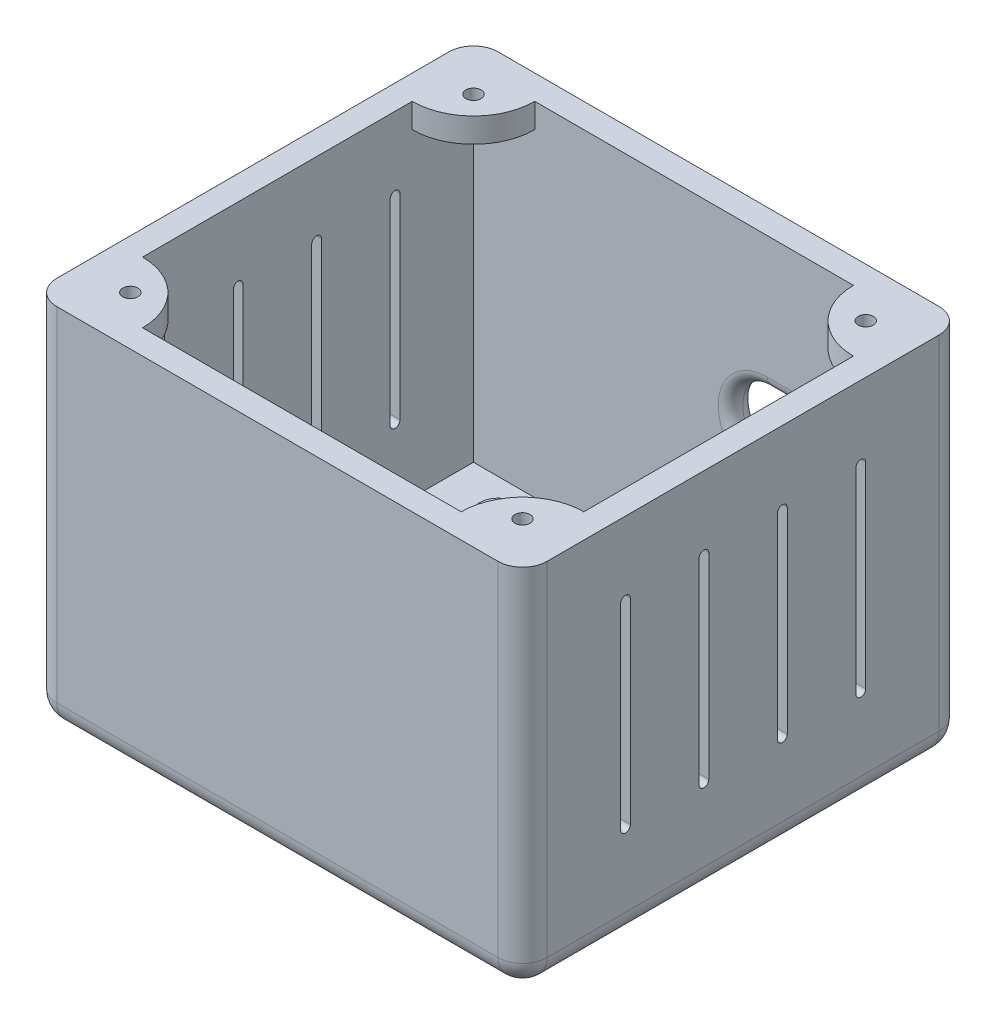
SolidWorks part; units mm, degrees
ref_plane "Front Plane" through (0, 0, 0) normal (0, 0, 1) x (1, 0, 0)
ref_plane "Top Plane" through (0, 0, 0) normal (0, 1, 0) x (1, 0, 0)
ref_plane "Right Plane" through (0, 0, 0) normal (1, 0, 0) x (0, 0, -1)
sketch "Sketch1" plane through (0, 0, 0) normal (0, 1, 0) x (1, 0, 0)
  line L0 (-5, 0) -> (0, 0) construction
  line L1 (0, 0) -> (90, 0)
  line L2 (0, 0) -> (0, 80)
  line L3 (0, 80) -> (90, 80)
  line L4 (90, 0) -> (90, 80)
  line L5 (-5, 85) -> (95, 85)
  line L6 (-5, 85) -> (-5, -5)
  line L7 (-5, -5) -> (95, -5)
  line L8 (95, 85) -> (95, -5)
  line L9 (0, 0) -> (0, -5) construction
  line L10 (90, 85) -> (90, 80) construction
  line L11 (90, 80) -> (95, 80) construction
  dimension "D1" = 90
  dimension "D2" = 5
  dimension "D3" = 80
extrude "Boss-Extrude1" add sketch "Sketch1" along normal blind 70
sketch "Sketch2" plane through (0, 0, 0) normal (0, -1, 0) x (-1, 0, 0)
  line L1 (5, -5) -> (-95, -5)
  line L2 (5, -5) -> (5, 85)
  line L3 (5, 85) -> (-95, 85)
  line L4 (-95, -5) -> (-95, 85)
extrude "Boss-Extrude2" add sketch "Sketch2" along normal blind 5
fillet "Fillet1" radius 5 4 edges at (-5, 32.5, -85) (95, 32.5, -85) (95, 32.5, 5) (-5, 32.5, 5)
sketch "Sketch3" plane through (0, 0, 0) normal (0, 1, 0) x (1, 0, 0)
  line L0 (16.5, 68.5) -> (16.5, 80) construction
  line L1 (90, 80) -> (0, 80) construction
  line L2 (16.5, 80) -> (0, 80) construction
  line L3 (73.5, 11.5) -> (73.5, 0) construction
  line L4 (0, 0) -> (90, 0) construction
  line L5 (73.5, 0) -> (90, 0) construction
  circle A0 centre (16.5, 68.5) radius 1.55
  circle A1 centre (16.5, 11.5) radius 1.55
  circle A2 centre (73.5, 11.5) radius 1.55
  circle A3 centre (73.5, 68.5) radius 1.55
  dimension "D3" = 3.1
  dimension "D1" = 57
  dimension "D2" = 57
extrude "Cut-Extrude1" cut sketch "Sketch3" against normal through all
sketch "Sketch4" plane through (0, -5, 0) normal (0, -1, 0) x (-1, 0, 0)
  circle A0 centre (-16.5, 11.5) radius 3
  circle A1 centre (-73.5, 11.5) radius 3
  circle A2 centre (-73.5, 68.5) radius 3
  circle A3 centre (-16.5, 68.5) radius 3
  dimension "D1" = 6
extrude "Cut-Extrude2" cut sketch "Sketch4" against normal blind 2.5
sketch "Sketch5" plane through (0, 0, 0) normal (0, 1, 0) x (1, 0, 0)
  line L0 (25, 65) -> (25, 15) construction
  line L1 (26, 65) -> (26, 15)
  line L2 (24, 65) -> (24, 15)
  line L3 (25, 65) -> (25, 80) construction
  line L6 (90, 80) -> (0, 80) construction
  line L7 (25, 15) -> (25, 0) construction
  line L8 (0, 0) -> (90, 0) construction
  line L9 (65, 65) -> (65, 15) construction
  line L11 (66, 65) -> (66, 15)
  line L12 (64, 65) -> (64, 15)
  line L13 (65, 65) -> (65, 80) construction
  line L14 (65, 15) -> (65, 0) construction
  line L15 (90, 80) -> (0, 80) construction
  line L16 (0, 0) -> (90, 0) construction
  line L17 (24, 65) -> (26, 65) construction
  line L18 (51.6667, 65) -> (51.6667, 15) construction
  line L19 (52.6667, 65) -> (52.6667, 15)
  line L20 (50.6667, 65) -> (50.6667, 15)
  line L21 (51.6667, 65) -> (51.6667, 80) construction
  line L22 (51.6667, 15) -> (51.6667, 0) construction
  line L23 (38.3333, 65) -> (38.3333, 15) construction
  line L24 (39.3333, 65) -> (39.3333, 15)
  line L25 (37.3333, 65) -> (37.3333, 15)
  line L26 (38.3333, 65) -> (38.3333, 80) construction
  line L27 (38.3333, 15) -> (38.3333, 0) construction
  line L28 (51.6667, 80) -> (65, 80) construction
  line L29 (38.3333, 80) -> (25, 80) construction
  line L30 (38.3333, 80) -> (51.6667, 80) construction
  line L31 (37.3333, 65) -> (39.3333, 65) construction
  line L32 (50.6667, 65) -> (52.6667, 65) construction
  line L33 (64, 65) -> (66, 65) construction
  line L34 (65, 80) -> (90, 80) construction
  line L35 (25, 80) -> (0, 80) construction
  arc A0 (26, 65) -> (24, 65) centre (25, 65) ccw
  arc A1 (24, 15) -> (26, 15) centre (25, 15) ccw
  arc A2 (66, 65) -> (64, 65) centre (65, 65) ccw
  arc A3 (64, 15) -> (66, 15) centre (65, 15) ccw
  arc A4 (52.6667, 65) -> (50.6667, 65) centre (51.6667, 65) ccw
  arc A5 (50.6667, 15) -> (52.6667, 15) centre (51.6667, 15) ccw
  arc A6 (39.3333, 65) -> (37.3333, 65) centre (38.3333, 65) ccw
  arc A7 (37.3333, 15) -> (39.3333, 15) centre (38.3333, 15) ccw
  point P2 (25, 40)
  point P19 (65, 40)
  point P37 (51.6667, 40)
  point P48 (38.3333, 40)
  dimension "D1" = 1
  dimension "D2" = 15
  dimension "D3" = 25
extrude "Cut-Extrude3" cut sketch "Sketch5" against normal through all
sketch "Sketch6" plane through (0, 0, -80) normal (0, 0, 1) x (1, 0, 0)
  line L0 (0, 70) -> (12.5, 70)
  line L1 (90, 70) -> (0, 70) construction
  line L3 (0, 70) -> (0, 0) construction
  line L4 (0, 65) -> (0, 70)
  line L5 (0, 65) -> (12.5, 65)
  line L6 (12.5, 65) -> (12.5, 70)
  dimension "D1" = 12.5
  dimension "D2" = 5
revolve "Revolve2" add sketch "Sketch6" angle 90 about axis through (0, 70, -80) along (0, -1, 0)
sketch "Sketch7" plane through (0, 0, -80) normal (0, 0, 1) x (1, 0, 0)
  line L1 (90, 70) -> (77.5, 70)
  line L2 (90, 70) -> (90, 65)
  line L3 (90, 65) -> (77.5, 65)
  line L4 (77.5, 70) -> (77.5, 65)
  dimension "D1" = 12.5
  dimension "D2" = 5
revolve "Revolve3" add sketch "Sketch7" angle 90 about axis through (90, 70, -80) along (0, -1, 0) reverse direction yes
sketch "Sketch8" plane through (0, 0, 0) normal (0, 0, -1) x (-1, 0, 0)
  line L1 (-90, 70) -> (-77.5, 70)
  line L2 (-90, 70) -> (-90, 65)
  line L3 (-90, 65) -> (-77.5, 65)
  line L4 (-77.5, 70) -> (-77.5, 65)
  dimension "D1" = 5
  dimension "D2" = 12.5
revolve "Revolve4" add sketch "Sketch8" angle 90 about axis through (90, 70, 0) along (0, -1, 0)
sketch "Sketch9" plane through (0, 0, 0) normal (0, 0, -1) x (-1, 0, 0)
  line L1 (0, 70) -> (-12.5, 70)
  line L2 (0, 70) -> (0, 65)
  line L3 (0, 65) -> (-12.5, 65)
  line L4 (-12.5, 70) -> (-12.5, 65)
  dimension "D1" = 12.5
  dimension "D2" = 5
revolve "Revolve5" add sketch "Sketch9" angle 90 about axis through (0, 70, 0) along (0, -1, 0) reverse direction yes
sketch "Sketch10" plane through (0, 70, 0) normal (0, 1, 0) x (1, 0, 0)
  line L0 (5, 75) -> (85, 75) construction
  line L1 (85, 75) -> (85, 5) construction
  line L2 (85, -5) -> (85, 85) construction
  line L4 (90, 85) -> (0, 85) construction
  line L6 (0, -5) -> (90, -5) construction
  line L8 (-5, 75) -> (95, 75) construction
  line L10 (95, 0) -> (95, 80) construction
  line L11 (-5, 80) -> (-5, 0) construction
  circle A0 centre (5, 75) radius 1.55
  circle A1 centre (85, 75) radius 1.55
  circle A2 centre (85, 5) radius 1.55
  circle A3 centre (5, 5) radius 1.55
  point P13 (85, 40)
  point P23 (45, 75)
  dimension "D2" = 3.1
  dimension "D1" = 80
  dimension "D3" = 70
extrude "Cut-Extrude5" cut sketch "Sketch10" against normal blind 5
sketch "Sketch13" plane through (0, 0, 0) normal (0, 1, 0) x (1, 0, 0)
  circle A0 centre (16.5, 68.5) radius 3.75
  circle A1 centre (73.5, 68.5) radius 3.75
  circle A2 centre (73.5, 11.5) radius 3.75
  circle A3 centre (16.5, 11.5) radius 3.75
  dimension "D1" = 7.5
extrude "Boss-Extrude3" add sketch "Sketch13" along normal blind 5
sketch "Sketch14" plane through (0, 0, 0) normal (0, -1, 0) x (-1, 0, 0)
  circle A0 centre (-73.5, 68.5) radius 1.55
  circle A1 centre (-73.5, 11.5) radius 1.55
  circle A2 centre (-16.5, 11.5) radius 1.55
  circle A3 centre (-16.5, 68.5) radius 1.55
extrude "Cut-Extrude7" cut sketch "Sketch14" against normal through all
fillet "Fillet3" radius 5 8 edges at (-3.5355, -5, -83.5355) (-3.5355, -5, 3.5355) (93.5355, -5, 3.5355) (93.5355, -5, -83.5355) (-5, -5, -40) (45, -5, 5) (95, -5, -40) (45, -5, -85)
sketch "Sketch15" plane through (0, 0, -85) normal (0, 0, -1) x (-1, 0, 0)
  line L0 (-65, 35) -> (-59.92, 35) construction
  line L1 (-65, 42.5) -> (-59.92, 42.5)
  line L2 (-65, 27.5) -> (-59.92, 27.5)
  line L3 (-90, 70) -> (-90, 0) construction
  line L4 (-90, 70) -> (0, 70) construction
  arc A1 (-65, 42.5) -> (-65, 27.5) centre (-65, 35) ccw
  arc A2 (-59.92, 27.5) -> (-59.92, 42.5) centre (-59.92, 35) ccw
  point P2 (-62.46, 35)
  dimension "D2" = 7.5
  dimension "D1" = 5.08
  dimension "D3" = 25
  dimension "D4" = 35
extrude "Cut-Extrude8" cut sketch "Sketch15" against normal up to surface (5 mm away) up to face at (45, 50, -80)
fillet "Fillet4" radius 2.5 8 edges at (62.46, 42.5, -85) (62.46, 27.5, -85) (62.46, 42.5, -80) (62.46, 27.5, -80) (52.42, 35, -85) (52.42, 35, -80) (72.5, 35, -85) (72.5, 35, -80)
sketch "Sketch16" plane through (-5, 0, 0) normal (1, 0, 0) x (0, 0, -1)
  line L0 (64, 55) -> (64, 15) construction
  line L7 (65, 55) -> (65, 15)
  line L12 (48, 15) -> (48, 55) construction
  line L20 (47, 15) -> (47, 55)
  line L22 (49, 15) -> (49, 55)
  line L23 (63, 55) -> (63, 15)
  line L24 (16, 55) -> (16, 15) construction
  line L25 (17, 55) -> (17, 15)
  line L26 (15, 55) -> (15, 15)
  line L27 (32, 55) -> (32, 15) construction
  line L28 (33, 55) -> (33, 15)
  line L29 (31, 55) -> (31, 15)
  line L30 (80, 55) -> (64, 55) construction
  line L31 (80, 70) -> (80, 0) construction
  line L32 (64, 55) -> (48, 55) construction
  line L33 (48, 55) -> (32, 55) construction
  line L34 (32, 55) -> (16, 55) construction
  line L35 (16, 55) -> (0, 55) construction
  line L36 (0, 0) -> (0, 70) construction
  line L37 (0, 15) -> (16, 15) construction
  line L38 (16, 15) -> (32, 15) construction
  line L39 (32, 15) -> (48, 15) construction
  line L40 (48, 15) -> (64, 15) construction
  line L41 (64, 15) -> (80, 15) construction
  line L42 (80, 55) -> (80, 70) construction
  line L43 (80, 15) -> (80, 0) construction
  arc A12 (65, 55) -> (63, 55) centre (64, 55) ccw
  arc A13 (63, 15) -> (65, 15) centre (64, 15) ccw
  arc A14 (47, 15) -> (49, 15) centre (48, 15) ccw
  arc A15 (49, 55) -> (47, 55) centre (48, 55) ccw
  arc A16 (17, 55) -> (15, 55) centre (16, 55) ccw
  arc A17 (15, 15) -> (17, 15) centre (16, 15) ccw
  arc A18 (33, 55) -> (31, 55) centre (32, 55) ccw
  arc A19 (31, 15) -> (33, 15) centre (32, 15) ccw
  point P2 (64, 35)
  point P7 (48, 35)
  point P14 (16, 35)
  point P21 (32, 35)
  dimension "D1" = 40
  dimension "D2" = 1
extrude "Cut-Extrude11" cut sketch "Sketch16" against normal through all and the other way through all
